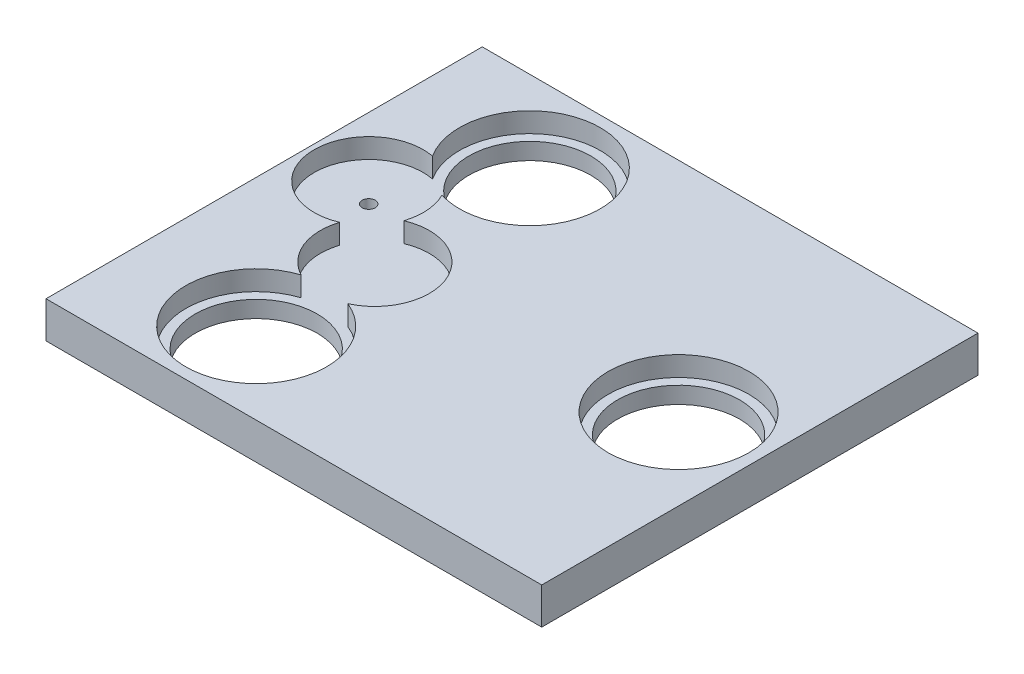
SolidWorks part; units mm, degrees
ref_plane "Front" through (0, 0, 0) normal (0, 0, 1) x (1, 0, 0)
ref_plane "Top" through (0, 0, 0) normal (0, 1, 0) x (1, 0, 0)
ref_plane "Right" through (0, 0, 0) normal (1, 0, 0) x (0, 0, -1)
sketch "Sketch1" plane through (0, 0, 0) normal (0, 1, 0) x (1, 0, 0)
  line L1 (-62.5, -55) -> (62.5, -55)
  line L2 (-62.5, -55) -> (-62.5, 55)
  line L3 (-62.5, 55) -> (62.5, 55)
  line L4 (62.5, -55) -> (62.5, 55)
  line L5 (-62.5, -55) -> (62.5, 55) construction
  line L6 (-62.5, 55) -> (62.5, -55) construction
  point P0 (0, 0)
  dimension "D1" = 125
  dimension "D2" = 110
extrude "Test_Base_Postion" add sketch "Sketch1" along normal blind 9.215
sketch "Thumb_Position" plane through (0, 9.215, 0) normal (0, 1, 0) x (1, 0, 0)
  line L0 (62.5, -55) -> (62.5, 55) construction
  line L1 (49, -12) -> (17, -12)
  line L2 (49, -12) -> (49, 43)
  line L3 (49, 43) -> (17, 43)
  line L4 (17, -12) -> (17, 43)
  line L5 (33, 43) -> (33, -12) construction
  line L6 (51, -12) -> (15, -12)
  line L7 (51, -12) -> (51, 12)
  line L8 (51, 12) -> (15, 12)
  line L9 (15, -12) -> (15, 12)
  line L10 (33, 12) -> (33, -12) construction
  line L11 (62.5, 55) -> (-62.5, 55) construction
  line L12 (51, 0) -> (15, 0) construction
  circle A1 centre (42, 0) radius 9
  circle A2 centre (42, 0) radius 17.75 construction
  dimension "D6" = 18
  dimension "D7" = 20.5
  dimension "D5" = 35.5
  dimension "D1" = 55
  dimension "D2" = 32
  dimension "D3" = 36
  dimension "D4" = 24
sketch "Finger_Gears_Position" plane through (0, 0, 0) normal (0, -1, 0) x (1, 0, 0)
  line L0 (-30, 34.5) -> (-30, 52) construction
  line L1 (-30, 34.5) -> (-47.5, 34.5) construction
  line L2 (-30, -34.5) -> (-30, -52) construction
  line L3 (-30, -34.5) -> (-47.5, -34.5) construction
  line L4 (-62.5, -55) -> (-62.5, 55) construction
  line L5 (-62.5, 55) -> (62.5, 55) construction
  line L8 (62.5, -55) -> (-62.5, -55) construction
  line L9 (-62.5, 0) -> (62.5, 0) construction
  line L10 (62.5, 55) -> (62.5, -55) construction
  line L13 (-30, -34.5) -> (-43, -34.5) construction
  line L15 (-43, -50.5) -> (12, -50.5) construction
  line L16 (-43, -50.5) -> (-43, -18.5) construction
  line L17 (-43, -18.5) -> (12, -18.5) construction
  line L18 (12, -50.5) -> (12, -18.5) construction
  line L20 (-30, 34.5) -> (-43, 34.5) construction
  line L21 (12, -34.5) -> (-23, -34.5) construction
  line L22 (-43, 18.5) -> (12, 18.5) construction
  line L23 (-43, 18.5) -> (-43, 50.5) construction
  line L24 (-43, 50.5) -> (12, 50.5) construction
  line L25 (12, 18.5) -> (12, 50.5) construction
  line L26 (12, 34.5) -> (-23, 34.5) construction
  line L27 (-23, -34.5) -> (-23, 34.5) construction
  circle A0 centre (-30, 34.5) radius 17.5 construction
  circle A1 centre (-30, -34.5) radius 17.5 construction
  dimension "D1" = 35
  dimension "D2" = 15
  dimension "D3" = 3
  dimension "D4" = 3
  dimension "D5" = 13
  dimension "D6" = 55
  dimension "D7" = 32
  dimension "D8" = 13
  dimension "D9" = 55
  dimension "D10" = 32
  dimension "D11" = 35
  dimension "D12" = 35
sketch "Fingers_Position" plane through (0, 9.215, 0) normal (0, 1, 0) x (1, 0, 0)
  line L0 (12, 34.5) -> (-23, 34.5) construction
  line L1 (12, 18.5) -> (-43, 18.5)
  line L2 (12, 18.5) -> (12, 50.5)
  line L3 (12, 50.5) -> (-43, 50.5)
  line L4 (-43, 18.5) -> (-43, 50.5)
  line L5 (12, -50.5) -> (-43, -50.5)
  line L6 (12, -50.5) -> (12, -18.5)
  line L7 (12, -18.5) -> (-43, -18.5)
  line L8 (-43, -50.5) -> (-43, -18.5)
  line L9 (-23, 34.5) -> (-23, -34.5) construction
  line L10 (-23, -34.5) -> (12, -34.5) construction
sketch "Thumb_Knuckle_Mount_Position" plane through (0, 0, 0) normal (0, -1, 0) x (1, 0, 0)
  circle A0 centre (42, 0) radius 17.75
  dimension "D1" = 35.5
sketch "Gears_Position" plane through (0, 0, 0) normal (0, -1, 0) x (-1, 0, 0)
  line L0 (30, 34.5) -> (30, 16) construction
  line L1 (30, 34.5) -> (30.5905, 19.0113) construction
  line L2 (30.7851, 18.0187) -> (29.2149, 18.0187) construction
  line L3 (31.4977, 16.0607) -> (30, 20.1757) construction
  line L4 (28.2415, 16.0838) -> (30, 34.5) construction
  line L5 (29.2149, 18.0187) -> (27.6518, 18.1679) construction
  line L6 (30, -34.5) -> (30, -53) construction
  line L7 (30.7851, -50.9813) -> (29.2149, -50.9813) construction
  line L8 (30.5905, -49.9887) -> (30, -34.5) construction
  line L9 (31.4977, -52.9393) -> (30, -48.8243) construction
  line L10 (30, -34.5) -> (28.2415, -52.9162) construction
  line L11 (29.2149, -50.9813) -> (27.6518, -50.8321) construction
  line L12 (47.5, 11.3753) -> (47.5, -3.1247) construction
  line L13 (47.5, 11.3753) -> (48.0842, -0.1098) construction
  line L14 (48.2849, -1.1) -> (46.7151, -1.1) construction
  line L15 (48.9937, -3.0475) -> (47.5, 1.0564) construction
  line L16 (47.5, 11.3753) -> (45.6827, -3.0103) construction
  line L17 (46.7151, -1.1) -> (45.1577, -0.9033) construction
  line L18 (29.8534, -17.9903) -> (28.2837, -17.9903) construction
  line L19 (29.0686, -5.515) -> (27.2512, -19.9006) construction
  line L20 (28.2837, -17.9903) -> (26.7263, -17.7936) construction
  line L21 (29.0686, -5.515) -> (29.0686, -20.015) construction
  line L22 (29.0686, -5.515) -> (29.6528, -17.0001) construction
  line L23 (30.5623, -19.9378) -> (29.0686, -15.8339) construction
  line L31 (62.5, 55) -> (62.5, -55) construction
  circle A0 centre (30, -34.5) radius 17.5 construction
  circle A1 centre (30, 34.5) radius 17.5 construction
  circle A2 centre (30, 34.5) radius 16.5
  circle A3 centre (30, 34.5) radius 15.5 construction
  circle A4 centre (30, 34.5) radius 18.5 construction
  arc A5 (32.4899, 16.1683) -> (30.5905, 19.0113) centre (33.854, 19.1357) cw
  arc A6 (27.5101, 16.1683) -> (29.4095, 19.0113) centre (26.146, 19.1357) ccw
  arc A7 (32.4899, -52.8317) -> (30.5905, -49.9887) centre (33.854, -49.8643) cw
  arc A8 (27.5101, -52.8317) -> (29.4095, -49.9887) centre (26.146, -49.8643) ccw
  circle A9 centre (30, -34.5) radius 16.5
  circle A10 centre (30, -34.5) radius 18.5 construction
  circle A11 centre (30, -34.5) radius 15.5 construction
  arc A12 (28.9757, -52.9716) -> (27.6486, -49.8206) centre (30.8766, -50.316) cw
  arc A13 (24.0858, -52.0292) -> (26.4889, -49.5971) centre (23.3079, -48.8573) ccw
  arc A14 (25.4984, -52.444) -> (24.7916, -49.0987) centre (27.8676, -50.1961) cw
  arc A15 (20.8752, -50.5931) -> (23.6952, -48.6598) centre (20.7117, -47.3314) ccw
  arc A16 (22.1838, -51.2678) -> (22.1229, -47.8492) centre (24.9356, -49.5089) cw
  arc A17 (17.9945, -48.5754) -> (21.1294, -47.2107) centre (18.4512, -45.3417) ccw
  arc A18 (19.1518, -49.4855) -> (19.7389, -46.1172) centre (22.1867, -48.2792) cw
  arc A19 (15.5476, -46.049) -> (18.8842, -45.3022) centre (16.6081, -42.9601) ccw
  arc A20 (16.5118, -47.1617) -> (17.7258, -43.9654) centre (19.7201, -46.5516) cw
  arc A21 (13.6232, -43.1052) -> (17.0407, -43.0033) centre (15.2491, -40.2728) ccw
  arc A22 (14.3593, -44.3802) -> (16.1562, -41.4714) centre (17.6251, -44.3883) cw
  arc A23 (12.2906, -39.8503) -> (15.6656, -40.3971) centre (14.4231, -37.3769) ccw
  arc A24 (12.7721, -41.2416) -> (15.0871, -38.7255) centre (15.9774, -41.8676) cw
  arc A25 (11.598, -36.4021) -> (14.8086, -37.5777) centre (14.1602, -34.3769) ccw
  arc A26 (11.8076, -37.8594) -> (14.5569, -35.8268) centre (14.8365, -39.0807) cw
  arc A27 (11.5706, -32.8851) -> (14.5007, -34.6471) centre (14.4697, -31.3814) ccw
  arc A28 (11.5006, -34.3557) -> (14.5849, -32.8802) centre (14.2436, -36.1282) cw
  arc A29 (12.2093, -29.4265) -> (14.7529, -31.7112) centre (15.3405, -28.4987) ccw
  arc A30 (11.8622, -30.8573) -> (15.17, -29.9922) centre (14.2202, -33.1169) cw
  arc A31 (13.4909, -26.1513) -> (15.5563, -28.8761) centre (16.7412, -25.8328) ccw
  arc A32 (12.8793, -27.4905) -> (16.2911, -27.267) centre (14.7671, -30.1555) cw
  arc A33 (15.3693, -23.1778) -> (16.8816, -26.2442) centre (18.6211, -23.4802) ccw
  arc A34 (14.5153, -24.3771) -> (17.9077, -24.8033) centre (15.8646, -27.3512) cw
  arc A35 (17.7764, -20.6135) -> (18.6811, -23.9107) centre (20.9122, -21.5259) ccw
  arc A36 (16.7109, -21.6295) -> (19.9613, -22.6901) centre (17.473, -24.8052) cw
  arc A37 (20.6253, -18.5511) -> (20.8897, -21.96) centre (23.5318, -20.0404) ccw
  arc A38 (19.3868, -19.3471) -> (22.3778, -21.0036) centre (19.5341, -22.6096) cw
  arc A39 (23.8131, -17.0652) -> (23.4275, -20.4625) centre (26.3852, -19.0776) ccw
  arc A40 (22.4463, -17.6124) -> (25.0697, -19.805) centre (21.9735, -20.8438) cw
  arc A41 (27.2245, -16.2094) -> (26.2029, -19.4723) centre (29.3693, -18.6722) ccw
  arc A42 (25.7788, -16.488) -> (27.9399, -19.1375) centre (24.703, -19.5716) cw
  arc A43 (30.7361, -16.0147) -> (29.1155, -19.0253) centre (32.3761, -18.8389) ccw
  arc A44 (29.2639, -16.0147) -> (30.8845, -19.0253) centre (27.6239, -18.8389) cw
  arc A45 (34.2212, -16.488) -> (32.0601, -19.1375) centre (35.297, -19.5716) ccw
  arc A46 (32.7755, -16.2094) -> (33.7971, -19.4723) centre (30.6307, -18.6722) cw
  arc A47 (37.5537, -17.6124) -> (34.9303, -19.805) centre (38.0265, -20.8438) ccw
  arc A48 (36.1869, -17.0652) -> (36.5725, -20.4625) centre (33.6148, -19.0776) cw
  arc A49 (40.6132, -19.3471) -> (37.6222, -21.0036) centre (40.4659, -22.6096) ccw
  arc A50 (39.3747, -18.5511) -> (39.1103, -21.96) centre (36.4682, -20.0404) cw
  arc A51 (43.2891, -21.6295) -> (40.0387, -22.6901) centre (42.527, -24.8052) ccw
  arc A52 (42.2236, -20.6135) -> (41.3189, -23.9107) centre (39.0878, -21.5259) cw
  arc A53 (45.4847, -24.3771) -> (42.0923, -24.8033) centre (44.1354, -27.3512) ccw
  arc A54 (44.6307, -23.1778) -> (43.1184, -26.2442) centre (41.3789, -23.4802) cw
  arc A55 (47.1207, -27.4905) -> (43.7089, -27.267) centre (45.2329, -30.1555) ccw
  arc A56 (46.5091, -26.1513) -> (44.4437, -28.8761) centre (43.2588, -25.8328) cw
  arc A57 (48.1378, -30.8573) -> (44.83, -29.9922) centre (45.7798, -33.1169) ccw
  arc A58 (47.7907, -29.4265) -> (45.2471, -31.7112) centre (44.6595, -28.4987) cw
  arc A59 (48.4994, -34.3557) -> (45.4151, -32.8802) centre (45.7564, -36.1282) ccw
  arc A60 (48.4294, -32.8851) -> (45.4993, -34.6471) centre (45.5303, -31.3814) cw
  arc A61 (48.1924, -37.8594) -> (45.4431, -35.8268) centre (45.1635, -39.0807) ccw
  arc A62 (48.402, -36.4021) -> (45.1914, -37.5777) centre (45.8398, -34.3769) cw
  arc A63 (47.2279, -41.2416) -> (44.9129, -38.7255) centre (44.0226, -41.8676) ccw
  arc A64 (47.7094, -39.8503) -> (44.3344, -40.3971) centre (45.5769, -37.3769) cw
  arc A65 (45.6407, -44.3802) -> (43.8438, -41.4714) centre (42.3749, -44.3883) ccw
  arc A66 (46.3768, -43.1052) -> (42.9593, -43.0033) centre (44.7509, -40.2728) cw
  arc A67 (43.4882, -47.1617) -> (42.2742, -43.9654) centre (40.2799, -46.5516) ccw
  arc A68 (44.4524, -46.049) -> (41.1158, -45.3022) centre (43.3919, -42.9601) cw
  arc A69 (40.8482, -49.4855) -> (40.2611, -46.1172) centre (37.8133, -48.2792) ccw
  arc A70 (42.0055, -48.5754) -> (38.8706, -47.2107) centre (41.5488, -45.3417) cw
  arc A71 (37.8162, -51.2678) -> (37.8771, -47.8492) centre (35.0644, -49.5089) ccw
  arc A72 (39.1248, -50.5931) -> (36.3048, -48.6598) centre (39.2883, -47.3314) cw
  arc A73 (34.5016, -52.444) -> (35.2084, -49.0987) centre (32.1324, -50.1961) ccw
  arc A74 (35.9142, -52.0292) -> (33.5111, -49.5971) centre (36.6921, -48.8573) cw
  arc A75 (31.0243, -52.9716) -> (32.3514, -49.8206) centre (29.1234, -50.316) ccw
  arc A76 (28.9757, 16.0284) -> (27.6486, 19.1794) centre (30.8766, 18.684) cw
  arc A77 (24.0858, 16.9708) -> (26.4889, 19.4029) centre (23.3079, 20.1427) ccw
  arc A78 (25.4984, 16.556) -> (24.7916, 19.9013) centre (27.8676, 18.8039) cw
  arc A79 (20.8752, 18.4069) -> (23.6952, 20.3402) centre (20.7117, 21.6686) ccw
  arc A80 (22.1838, 17.7322) -> (22.1229, 21.1508) centre (24.9356, 19.4911) cw
  arc A81 (17.9945, 20.4246) -> (21.1294, 21.7893) centre (18.4512, 23.6583) ccw
  arc A82 (19.1518, 19.5145) -> (19.7389, 22.8828) centre (22.1867, 20.7208) cw
  arc A83 (15.5476, 22.951) -> (18.8842, 23.6978) centre (16.6081, 26.0399) ccw
  arc A84 (16.5118, 21.8383) -> (17.7258, 25.0346) centre (19.7201, 22.4484) cw
  arc A85 (13.6232, 25.8948) -> (17.0407, 25.9967) centre (15.2491, 28.7272) ccw
  arc A86 (14.3593, 24.6198) -> (16.1562, 27.5286) centre (17.6251, 24.6117) cw
  arc A87 (12.2906, 29.1497) -> (15.6656, 28.6029) centre (14.4231, 31.6231) ccw
  arc A88 (12.7721, 27.7584) -> (15.0871, 30.2745) centre (15.9774, 27.1324) cw
  arc A89 (11.598, 32.5979) -> (14.8086, 31.4223) centre (14.1602, 34.6231) ccw
  arc A90 (11.8076, 31.1406) -> (14.5569, 33.1732) centre (14.8365, 29.9193) cw
  arc A91 (11.5706, 36.1149) -> (14.5007, 34.3529) centre (14.4697, 37.6186) ccw
  arc A92 (11.5006, 34.6443) -> (14.5849, 36.1198) centre (14.2436, 32.8718) cw
  arc A93 (12.2093, 39.5735) -> (14.7529, 37.2888) centre (15.3405, 40.5013) ccw
  arc A94 (11.8622, 38.1427) -> (15.17, 39.0078) centre (14.2202, 35.8831) cw
  arc A95 (13.4909, 42.8487) -> (15.5563, 40.1239) centre (16.7412, 43.1672) ccw
  arc A96 (12.8793, 41.5095) -> (16.2911, 41.733) centre (14.7671, 38.8445) cw
  arc A97 (15.3693, 45.8222) -> (16.8816, 42.7558) centre (18.6211, 45.5198) ccw
  arc A98 (14.5153, 44.6229) -> (17.9077, 44.1967) centre (15.8646, 41.6488) cw
  arc A99 (17.7764, 48.3865) -> (18.6811, 45.0893) centre (20.9122, 47.4741) ccw
  arc A100 (16.7109, 47.3705) -> (19.9613, 46.3099) centre (17.473, 44.1948) cw
  arc A101 (20.6253, 50.4489) -> (20.8897, 47.04) centre (23.5318, 48.9596) ccw
  arc A102 (19.3868, 49.6529) -> (22.3778, 47.9964) centre (19.5341, 46.3904) cw
  arc A103 (23.8131, 51.9348) -> (23.4275, 48.5375) centre (26.3852, 49.9224) ccw
  arc A104 (22.4463, 51.3876) -> (25.0697, 49.195) centre (21.9735, 48.1562) cw
  arc A105 (27.2245, 52.7906) -> (26.2029, 49.5277) centre (29.3693, 50.3278) ccw
  arc A106 (25.7788, 52.512) -> (27.9399, 49.8625) centre (24.703, 49.4284) cw
  arc A107 (30.7361, 52.9853) -> (29.1155, 49.9747) centre (32.3761, 50.1611) ccw
  arc A108 (29.2639, 52.9853) -> (30.8845, 49.9747) centre (27.6239, 50.1611) cw
  arc A109 (34.2212, 52.512) -> (32.0601, 49.8625) centre (35.297, 49.4284) ccw
  arc A110 (32.7755, 52.7906) -> (33.7971, 49.5277) centre (30.6307, 50.3278) cw
  arc A111 (37.5537, 51.3876) -> (34.9303, 49.195) centre (38.0265, 48.1562) ccw
  arc A112 (36.1869, 51.9348) -> (36.5725, 48.5375) centre (33.6148, 49.9224) cw
  arc A113 (40.6132, 49.6529) -> (37.6222, 47.9964) centre (40.4659, 46.3904) ccw
  arc A114 (39.3747, 50.4489) -> (39.1103, 47.04) centre (36.4682, 48.9596) cw
  arc A115 (43.2891, 47.3705) -> (40.0387, 46.3099) centre (42.527, 44.1948) ccw
  arc A116 (42.2236, 48.3865) -> (41.3189, 45.0893) centre (39.0878, 47.4741) cw
  arc A117 (45.4847, 44.6229) -> (42.0923, 44.1967) centre (44.1354, 41.6488) ccw
  arc A118 (44.6307, 45.8222) -> (43.1184, 42.7558) centre (41.3789, 45.5198) cw
  arc A119 (47.1207, 41.5095) -> (43.7089, 41.733) centre (45.2329, 38.8445) ccw
  arc A120 (46.5091, 42.8487) -> (44.4437, 40.1239) centre (43.2588, 43.1672) cw
  arc A121 (48.1378, 38.1427) -> (44.83, 39.0078) centre (45.7798, 35.8831) ccw
  arc A122 (47.7907, 39.5735) -> (45.2471, 37.2888) centre (44.6595, 40.5013) cw
  arc A123 (48.4994, 34.6443) -> (45.4151, 36.1198) centre (45.7564, 32.8718) ccw
  arc A124 (48.4294, 36.1149) -> (45.4993, 34.3529) centre (45.5303, 37.6186) cw
  arc A125 (48.1924, 31.1406) -> (45.4431, 33.1732) centre (45.1635, 29.9193) ccw
  arc A126 (48.402, 32.5979) -> (45.1914, 31.4223) centre (45.8398, 34.6231) cw
  arc A127 (47.2279, 27.7584) -> (44.9129, 30.2745) centre (44.0226, 27.1324) ccw
  arc A128 (47.7094, 29.1497) -> (44.3344, 28.6029) centre (45.5769, 31.6231) cw
  arc A129 (45.6407, 24.6198) -> (43.8438, 27.5286) centre (42.3749, 24.6117) ccw
  arc A130 (46.3768, 25.8948) -> (42.9593, 25.9967) centre (44.7509, 28.7272) cw
  arc A131 (43.4882, 21.8383) -> (42.2742, 25.0346) centre (40.2799, 22.4484) ccw
  arc A132 (44.4524, 22.951) -> (41.1158, 23.6978) centre (43.3919, 26.0399) cw
  arc A133 (40.8482, 19.5145) -> (40.2611, 22.8828) centre (37.8133, 20.7208) ccw
  arc A134 (42.0055, 20.4246) -> (38.8706, 21.7893) centre (41.5488, 23.6583) cw
  arc A135 (37.8162, 17.7322) -> (37.8771, 21.1508) centre (35.0644, 19.4911) ccw
  arc A136 (39.1248, 18.4069) -> (36.3048, 20.3402) centre (39.2883, 21.6686) cw
  arc A137 (34.5016, 16.556) -> (35.2084, 19.9013) centre (32.1324, 18.8039) ccw
  arc A138 (35.9142, 16.9708) -> (33.5111, 19.4029) centre (36.6921, 20.1427) cw
  arc A139 (31.0243, 16.0284) -> (32.3514, 19.1794) centre (29.1234, 18.684) ccw
  circle A140 centre (47.5, 11.3753) radius 11.5 construction
  circle A141 centre (47.5, 11.3753) radius 12.5
  circle A142 centre (47.5, 11.3753) radius 13.5 construction
  circle A143 centre (47.5, 11.3753) radius 14.5 construction
  arc A144 (49.8668, -2.9302) -> (48.0842, -0.1098) centre (51.48, 0.0629) cw
  arc A145 (45.1332, -2.9302) -> (46.9158, -0.1098) centre (43.52, 0.0629) ccw
  arc A146 (26.7017, -19.8205) -> (28.4843, -17.0001) centre (25.0886, -16.8274) ccw
  circle A147 centre (29.0686, -5.515) radius 11.5 construction
  circle A148 centre (29.0686, -5.515) radius 12.5
  arc A149 (31.4354, -19.8205) -> (29.6528, -17.0001) centre (33.0485, -16.8274) cw
  circle A150 centre (29.0686, -5.515) radius 13.5 construction
  circle A151 centre (29.0686, -5.515) radius 14.5 construction
  arc A152 (46.2348, -3.0694) -> (45.2096, 0.1057) centre (48.5416, -0.5715) cw
  arc A153 (41.6499, -1.8922) -> (44.0779, 0.3963) centre (40.8318, 1.4081) ccw
  arc A154 (42.6823, -2.3009) -> (42.4789, 1.0294) centre (45.5379, -0.4552) cw
  arc A155 (38.5342, -0.0205) -> (41.455, 1.5923) centre (38.5625, 3.3796) ccw
  arc A156 (39.4325, -0.6731) -> (40.0638, 2.6031) centre (42.6574, 0.4045) cw
  arc A157 (35.9819, 2.5673) -> (39.212, 3.4029) centre (36.8548, 5.8534) ccw
  arc A158 (36.6896, 1.7117) -> (38.1158, 4.728) centre (40.0812, 1.9534) cw
  arc A159 (34.1532, 5.7084) -> (37.4897, 5.7146) centre (35.816, 8.6742) ccw
  arc A160 (34.626, 4.7037) -> (36.7575, 7.2706) centre (37.9711, 4.0944) cw
  arc A161 (33.1632, 9.2057) -> (36.3964, 8.3819) centre (35.5114, 11.6648) ccw
  arc A162 (33.3713, 8.1149) -> (36.0742, 10.0711) centre (36.4598, 6.6929) cw
  arc A163 (33.0741, 12.8392) -> (36.0008, 11.2372) centre (35.96, 14.6371) ccw
  arc A164 (33.0044, 11.731) -> (36.1088, 12.9536) centre (35.6422, 9.5856) cw
  arc A165 (33.8914, 16.3808) -> (36.3278, 14.1013) centre (37.1337, 17.4045) ccw
  arc A166 (33.5482, 15.3248) -> (36.8592, 15.7369) centre (35.5696, 12.5908) cw
  arc A167 (35.5637, 19.6079) -> (37.3567, 16.7941) centre (38.9588, 19.7931) ccw
  arc A168 (34.9687, 18.6704) -> (38.2781, 18.2461) centre (36.2467, 15.5195) cw
  arc A169 (37.9861, 22.3177) -> (39.0229, 19.1464) centre (41.3206, 21.6528) ccw
  arc A170 (37.1766, 21.5576) -> (40.2766, 20.3236) centre (37.6309, 18.1879) cw
  arc A171 (41.0062, 24.3399) -> (41.2218, 21.0104) centre (44.0706, 22.8666) ccw
  arc A172 (40.0332, 23.805) -> (42.7288, 21.8389) centre (39.6351, 20.4282) cw
  arc A173 (44.4344, 25.5476) -> (43.8152, 22.269) centre (47.0361, 23.3585) ccw
  arc A174 (43.3589, 25.2714) -> (45.4809, 22.6967) centre (42.1336, 22.0997) cw
  arc A175 (48.0552, 25.8647) -> (46.6401, 22.8431) centre (50.0308, 23.0974) ccw
  arc A176 (46.9448, 25.8647) -> (48.3599, 22.8431) centre (44.9692, 23.0974) cw
  arc A177 (51.6411, 25.2714) -> (49.5191, 22.6967) centre (52.8664, 22.0997) ccw
  arc A178 (50.5656, 25.5476) -> (51.1848, 22.269) centre (47.9639, 23.3585) cw
  arc A179 (54.9668, 23.805) -> (52.2712, 21.8389) centre (55.3649, 20.4282) ccw
  arc A180 (53.9938, 24.3399) -> (53.7782, 21.0104) centre (50.9294, 22.8666) cw
  arc A181 (57.8234, 21.5576) -> (54.7234, 20.3236) centre (57.3691, 18.1879) ccw
  arc A182 (57.0139, 22.3177) -> (55.9771, 19.1464) centre (53.6794, 21.6528) cw
  arc A183 (60.0313, 18.6704) -> (56.7219, 18.2461) centre (58.7533, 15.5195) ccw
  arc A184 (59.4363, 19.6079) -> (57.6433, 16.7941) centre (56.0412, 19.7931) cw
  arc A185 (61.4518, 15.3248) -> (58.1408, 15.7369) centre (59.4304, 12.5908) ccw
  arc A186 (61.1086, 16.3808) -> (58.6722, 14.1013) centre (57.8663, 17.4045) cw
  arc A187 (61.9956, 11.731) -> (58.8912, 12.9536) centre (59.3578, 9.5856) ccw
  arc A188 (61.9259, 12.8392) -> (58.9992, 11.2372) centre (59.04, 14.6371) cw
  arc A189 (61.6287, 8.1149) -> (58.9258, 10.0711) centre (58.5402, 6.6929) ccw
  arc A190 (61.8368, 9.2057) -> (58.6036, 8.3819) centre (59.4886, 11.6648) cw
  arc A191 (60.374, 4.7037) -> (58.2425, 7.2706) centre (57.0289, 4.0944) ccw
  arc A192 (60.8468, 5.7084) -> (57.5103, 5.7146) centre (59.184, 8.6742) cw
  arc A193 (58.3104, 1.7117) -> (56.8842, 4.728) centre (54.9188, 1.9534) ccw
  arc A194 (59.0181, 2.5673) -> (55.788, 3.4029) centre (58.1452, 5.8534) cw
  arc A195 (55.5675, -0.6731) -> (54.9362, 2.6031) centre (52.3426, 0.4045) ccw
  arc A196 (56.4658, -0.0205) -> (53.545, 1.5923) centre (56.4375, 3.3796) cw
  arc A197 (52.3177, -2.3009) -> (52.5211, 1.0294) centre (49.4621, -0.4552) ccw
  arc A198 (53.3501, -1.8922) -> (50.9221, 0.3963) centre (54.1682, 1.4081) cw
  arc A199 (48.7652, -3.0694) -> (49.7904, 0.1057) centre (46.4584, -0.5715) ccw
  arc A200 (23.2185, -18.7825) -> (25.6465, -16.494) centre (22.4004, -15.4822) ccw
  arc A201 (27.8034, -19.9597) -> (26.7782, -16.7846) centre (30.1102, -17.4618) cw
  arc A202 (20.1028, -16.9108) -> (23.0236, -15.298) centre (20.1311, -13.5107) ccw
  arc A203 (24.2509, -19.1912) -> (24.0475, -15.8609) centre (27.1064, -17.3455) cw
  arc A204 (17.5504, -14.323) -> (20.7806, -13.4874) centre (18.4234, -11.0369) ccw
  arc A205 (21.0011, -17.5634) -> (21.6323, -14.2872) centre (24.226, -16.4858) cw
  arc A206 (15.7218, -11.1819) -> (19.0583, -11.1757) centre (17.3846, -8.2161) ccw
  arc A207 (18.2582, -15.1786) -> (19.6844, -12.1623) centre (21.6497, -14.9369) cw
  arc A208 (14.7318, -7.6846) -> (17.965, -8.5084) centre (17.0799, -5.2255) ccw
  arc A209 (16.1946, -12.1866) -> (18.3261, -9.6197) centre (19.5397, -12.7959) cw
  arc A210 (14.6427, -4.0511) -> (17.5694, -5.6531) centre (17.5286, -2.2532) ccw
  arc A211 (14.9399, -8.7754) -> (17.6428, -6.8192) centre (18.0284, -10.1974) cw
  arc A212 (15.4599, -0.5095) -> (17.8963, -2.789) centre (18.7023, 0.5142) ccw
  arc A213 (14.5729, -5.1593) -> (17.6774, -3.9367) centre (17.2108, -7.3047) cw
  arc A214 (17.1323, 2.7176) -> (18.9252, -0.0962) centre (20.5274, 2.9028) ccw
  arc A215 (15.1168, -1.5655) -> (18.4277, -1.1534) centre (17.1382, -4.2995) cw
  arc A216 (19.5546, 5.4274) -> (20.5915, 2.2561) centre (22.8891, 4.7625) ccw
  arc A217 (16.5373, 1.7801) -> (19.8467, 1.3558) centre (17.8153, -1.3708) cw
  arc A218 (22.5748, 7.4496) -> (22.7904, 4.1201) centre (25.6392, 5.9763) ccw
  arc A219 (18.7452, 4.6673) -> (21.8451, 3.4333) centre (19.1994, 1.2976) cw
  arc A220 (26.003, 8.6573) -> (25.3838, 5.3787) centre (28.6047, 6.4682) ccw
  arc A221 (21.6017, 6.9147) -> (24.2974, 4.9486) centre (21.2037, 3.5379) cw
  arc A222 (29.6238, 8.9744) -> (28.2087, 5.9528) centre (31.5993, 6.2071) ccw
  arc A223 (24.9274, 8.3811) -> (27.0495, 5.8064) centre (23.7022, 5.2094) cw
  arc A224 (33.2097, 8.3811) -> (31.0876, 5.8064) centre (34.435, 5.2094) ccw
  arc A225 (28.5134, 8.9744) -> (29.9284, 5.9528) centre (26.5378, 6.2071) cw
  arc A226 (36.5354, 6.9147) -> (33.8397, 4.9486) centre (36.9334, 3.5379) ccw
  arc A227 (32.1342, 8.6573) -> (32.7533, 5.3787) centre (29.5325, 6.4682) cw
  arc A228 (39.3919, 4.6673) -> (36.292, 3.4333) centre (38.9377, 1.2976) ccw
  arc A229 (35.5623, 7.4496) -> (35.3467, 4.1201) centre (32.498, 5.9763) cw
  arc A230 (41.5998, 1.7801) -> (38.2904, 1.3558) centre (40.3219, -1.3708) ccw
  arc A231 (38.5825, 5.4274) -> (37.5456, 2.2561) centre (35.248, 4.7625) cw
  arc A232 (43.0203, -1.5655) -> (39.7094, -1.1534) centre (40.9989, -4.2995) ccw
  arc A233 (41.0049, 2.7176) -> (39.2119, -0.0962) centre (37.6098, 2.9028) cw
  arc A234 (43.5642, -5.1593) -> (40.4598, -3.9367) centre (40.9264, -7.3047) ccw
  arc A235 (42.6772, -0.5095) -> (40.2408, -2.789) centre (39.4348, 0.5142) cw
  arc A236 (43.1973, -8.7754) -> (40.4944, -6.8192) centre (40.1088, -10.1974) ccw
  arc A237 (43.4945, -4.0511) -> (40.5677, -5.6531) centre (40.6086, -2.2532) cw
  arc A238 (41.9425, -12.1866) -> (39.8111, -9.6197) centre (38.5974, -12.7959) ccw
  arc A239 (43.4053, -7.6846) -> (40.1721, -8.5084) centre (41.0572, -5.2255) cw
  arc A240 (39.8789, -15.1786) -> (38.4528, -12.1623) centre (36.4874, -14.9369) ccw
  arc A241 (42.4153, -11.1819) -> (39.0788, -11.1757) centre (40.7525, -8.2161) cw
  arc A242 (37.136, -17.5634) -> (36.5048, -14.2872) centre (33.9112, -16.4858) ccw
  arc A243 (40.5867, -14.323) -> (37.3566, -13.4874) centre (39.7137, -11.0369) cw
  arc A244 (33.8862, -19.1912) -> (34.0896, -15.8609) centre (31.0307, -17.3455) ccw
  arc A245 (38.0344, -16.9108) -> (35.1135, -15.298) centre (38.006, -13.5107) cw
  arc A246 (30.3337, -19.9597) -> (31.3589, -16.7846) centre (28.0269, -17.4618) ccw
  arc A247 (34.9187, -18.7825) -> (32.4907, -16.494) centre (35.7368, -15.4822) cw
  point P233 (30, -34.5)
  point P426 (30, 34.5)
  point P607 (47.5, 11.3753)
  point P753 (29.0686, -5.515)
  dimension "D1" = 35
  dimension "D2" = 31
  dimension "D3" = 33
  dimension "D4" = 37
  dimension "D7" = 37
  dimension "D8" = 33
  dimension "D9" = 31
  dimension "D14" = 23
  dimension "D15" = 25
  dimension "D16" = 27
  dimension "D17" = 29
  dimension "D20" = 23
  dimension "D21" = 25
  dimension "D22" = 27
  dimension "D23" = 29
  dimension "D5" = 20
  dimension "D6" = 5.455
  dimension "D10" = 20
  dimension "D11" = 5.455
  dimension "D18" = 20
  dimension "D19" = 7.2
  dimension "D24" = 20
  dimension "D25" = 7.2
  dimension "D31" = 15
  dimension "D12" = 33
  dimension "D13" = 33
  dimension "D26" = 25
  dimension "D27" = 25
sketch "Sketch7" plane through (0, 0, 0) normal (0, -1, 0) x (1, 0, 0)
  circle A0 centre (42, 0) radius 17.75
  dimension "D1" = 35.5
extrude "Thumb_Knuckle_Mount" cut sketch "Sketch7" against normal up to surface (9.215 mm away) from offset 4.215 up to face at (0, 9.215, 0) offset against normal yes
sketch "Sketch8" plane through (0, 0, 0) normal (0, -1, 0) x (1, 0, 0)
  circle A0 centre (42, 0) radius 15.375
  dimension "D1" = 30.75
extrude "Thumb_Knuckle" cut sketch "Sketch8" along direction (0, -1, 0) on the side against the normal up to surface (4.215 mm away) up to face at (42, 4.215, -17.75)
sketch "Sketch10" plane through (0, 0, 0) normal (0, -1, 0) x (1, 0, 0)
  circle A0 centre (-30, 34.5) radius 17.75
  circle A1 centre (-29.0686, 5.515) radius 13.75
  circle A2 centre (-47.5, -11.3753) radius 13.75
  circle A3 centre (-30, -34.5) radius 17.75
  dimension "D1" = 35.5
  dimension "D2" = 27.5
extrude "Gears_Position_Extrude_Cut" cut sketch "Sketch10" against normal up to surface (9.215 mm away) from offset 4.215 contours A1 A0 | A2 A1 A0 | A3 A2 A1 | A2 A3 | A0 A1 | A1 A2 | A2 A3 region at (-30.0112, 0, 34.8491) region at (-29.469, 0, 17.9762) region at (-28.7333, 0, 5.3482) region at (-38.2843, 0, -2.9302) region at (-48.0986, 0, -11.3016) region at (-39.9764, 0, -21.317) region at (-29.7892, 0, -34.7785) up to face at (42, 9.215, -17.75) offset against normal yes
sketch "Sketch11" plane through (0, 0, 0) normal (0, -1, 0) x (1, 0, 0)
  circle A0 centre (-30, 34.5) radius 15.375
  circle A1 centre (-30, -34.5) radius 15.375
  circle A2 centre (-47.5, -11.3753) radius 1.65
  circle A3 centre (-30, 34.5) radius 17.75 construction
  circle A4 centre (-30, -34.5) radius 17.75 construction
  circle A5 centre (-47.5, -11.3753) radius 13.75 construction
  dimension "D1" = 3.3
  dimension "D2" = 30.75
extrude "Fingers_Knuckle_Mount_and_Intermediate_Through_Hole" cut sketch "Sketch11" against normal through all
equation "\"D6@Gears_Position\"=180/33"
equation "\"D11@Gears_Position\"=180/33"
equation "\"D19@Gears_Position\"=180/25"
